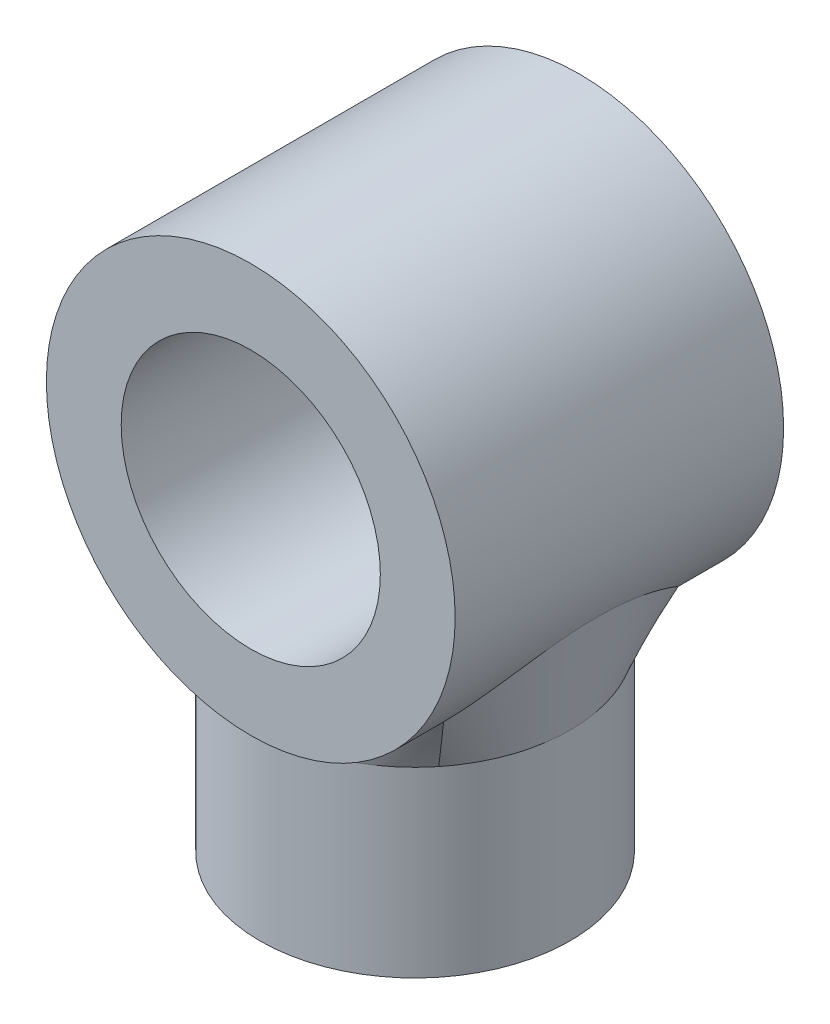
SolidWorks part; units mm, degrees
ref_plane "Front Plane" through (0, 0, 0) normal (0, 0, 1) x (1, 0, 0)
ref_plane "Top Plane" through (0, 0, 0) normal (0, 1, 0) x (1, 0, 0)
ref_plane "Right Plane" through (0, 0, 0) normal (1, 0, 0) x (0, 0, -1)
sketch "Sketch1" plane through (0, 0, 0) normal (0, 1, 0) x (1, 0, 0)
  circle A0 centre (0, 0) radius 6
  circle A1 centre (0, 0) radius 8.5
  dimension "D1" = 12
  dimension "D2" = 17
extrude "Boss-Extrude1" add sketch "Sketch1" along normal blind 10
sketch "Sketch3" plane through (0, 0, 0) normal (0, 0, 1) x (1, 0, 0)
  line L0 (8.5, 10) -> (-8.5, 10) construction
  circle A1 centre (0, 21.2) radius 11.2
  dimension "D2" = 22.4
extrude "Boss-Extrude2" add sketch "Sketch3" along normal blind 9 and the other way blind 9 separate body
ref_point "Point1"
ref_plane "Plane1" through (0, 21.2, 0) normal (0, 1, 0) x (1, 0, 0)
sketch "Sketch6" plane through (0, 10, 0) normal (0, 1, 0) x (1, 0, 0)
  circle A0 centre (0, 0) radius 8.5
  circle A1 centre (0, 0) radius 8.5 construction
sketch "Sketch7" plane through (0, 21.2, 0) normal (0, 1, 0) x (1, 0, 0)
  line L1 (-11.2, -9) -> (11.2, -9)
  line L2 (-11.2, -9) -> (-11.2, 9)
  line L3 (-11.2, 9) -> (11.2, 9)
  line L4 (11.2, -9) -> (11.2, 9)
  line L5 (-11.2, -9) -> (11.2, 9) construction
  line L6 (-11.2, 9) -> (11.2, -9) construction
  point P0 (0, 0)
loft "Loft1" add profiles "Sketch7", "Sketch6" connector at (-11.2, 21.2, -9) connector at (0, 10, 8.5)
sketch "Sketch8" plane through (0, 0, 9) normal (0, 0, 1) x (1, 0, 0)
  line L0 (9.35, 21.2) -> (-9.35, 21.2) construction
  circle A0 centre (0, 21.2) radius 7.1
  circle A1 centre (0, 21.2) radius 11.2 construction
  dimension "D1" = 14.2
extrude "Cut-Extrude1" cut sketch "Sketch8" against normal up to surface (18 mm away) up to face at (11.2, 21.2, -9)
equation "\"pin_bore\"=14.20"
equation "\"top_outer_diameter\"=22.40"
equation "\"D2@Sketch3\"=\"top_outer_diameter\""
equation "\"D1@Sketch8\"=\"pin_bore\""
equation "\"bottom_height\"=23.10"
equation "\"bottom_bore_height\"=11.90"
